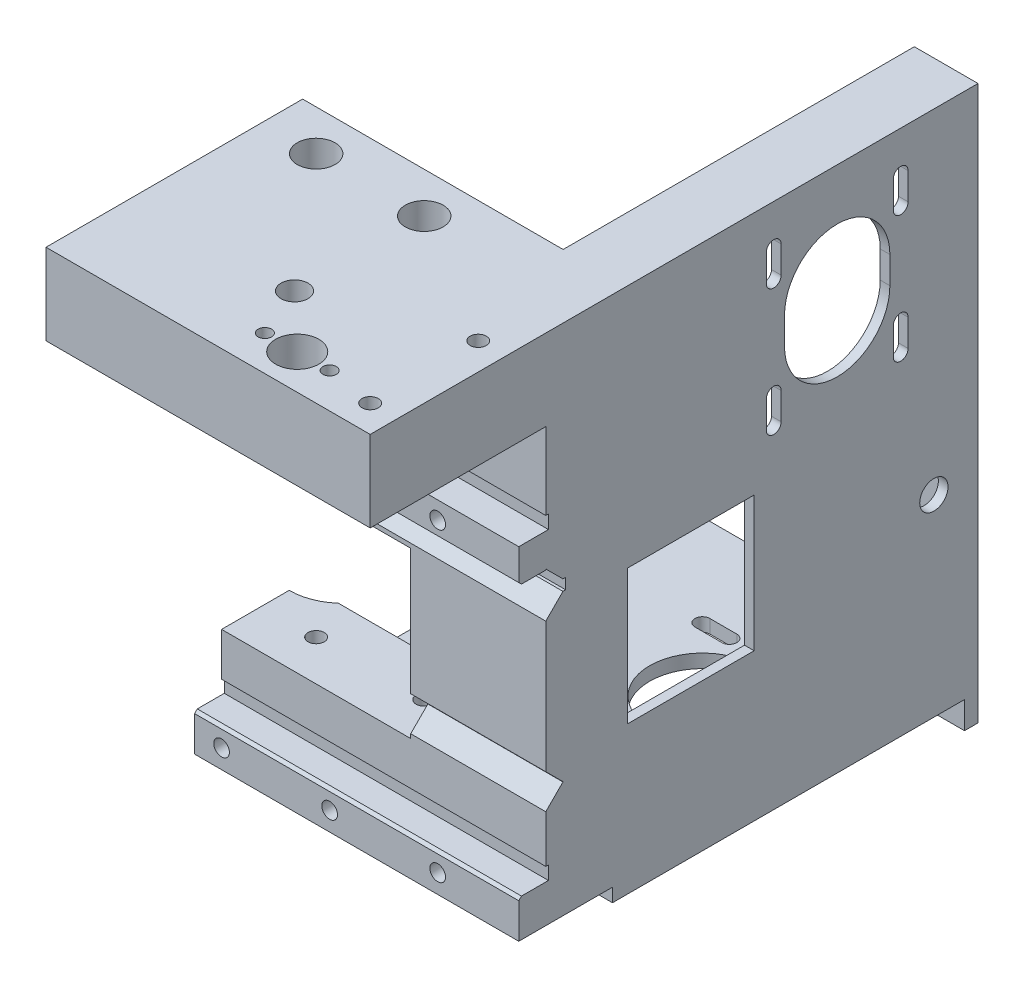
SolidWorks part; units mm, degrees
material "ABS"
ref_plane "Front Plane" through (0, 0, 0) normal (0, 0, 1) x (1, 0, 0)
ref_plane "Top Plane" through (0, 0, 0) normal (0, 1, 0) x (1, 0, 0)
ref_plane "Right Plane" through (0, 0, 0) normal (1, 0, 0) x (0, 0, -1)
sketch "Sketch1" plane through (0, 0, 0) normal (0, 0, 1) x (1, 0, 0)
  line L0 (-43.1034, -43.5723) -> (-43.1034, -8.5723)
  line L1 (-43.1034, 146.4277) -> (76.8966, 146.4277)
  line L2 (-43.1034, 146.4277) -> (-43.1034, 52.4277)
  line L3 (-43.1034, -43.5723) -> (76.8966, -43.5723)
  line L4 (76.8966, 146.4277) -> (76.8966, -43.5723)
  line L5 (-43.1034, 52.4277) -> (26.8966, 52.4277)
  line L7 (-43.1034, -8.5723) -> (26.8966, -8.5723)
  line L8 (26.8966, 52.4277) -> (26.8966, -8.5723)
  dimension "D1" = 61
  dimension "D2" = 190
  dimension "D3" = 35
  dimension "D4" = 120
  dimension "D6" = 70
extrude "Boss-Extrude1" add sketch "Sketch1" along normal blind 30
sketch "Sketch2" plane through (-43.1034, 0, 0) normal (-1, 0, 0) x (0, 0, 1)
  line L0 (30, 5.7917) -> (23.636, -0.5723)
  line L1 (30, 146.4277) -> (30, 52.4277) construction
  line L2 (23.636, -0.5723) -> (23.636, -0.6723)
  line L3 (23.636, -0.6723) -> (30, -7.0362)
  line L4 (30, -7.0362) -> (30, 5.7917)
  line L5 (30, -43.5723) -> (0, -43.5723) construction
  line L6 (30, 70.7917) -> (23.636, 64.4277)
  line L7 (30, -24.5723) -> (29, -24.5723)
  line L8 (30, -24.5723) -> (30, -29.5723)
  line L9 (30, -29.5723) -> (29, -29.5723)
  line L10 (29, -24.5723) -> (29, -29.5723)
  line L11 (23.636, 64.4277) -> (22.636, 64.4277)
  line L12 (22.636, 64.4277) -> (22.636, 60.4277)
  line L13 (22.636, 60.4277) -> (23.636, 60.4277)
  line L14 (23.636, 60.4277) -> (30, 54.0638)
  line L15 (30, 54.0638) -> (30, 70.7917)
  point P13 (29.5, -29.5723)
  dimension "D1" = 9
  dimension "D2" = 9
  dimension "D3" = 0.1
  dimension "D4" = 43
  dimension "D5" = 135
  dimension "D6" = 90
  dimension "D7" = 5
  dimension "D8" = 14
  dimension "D9" = 1
  dimension "D10" = 9
  dimension "D11" = 9
  dimension "D12" = 135
  dimension "D13" = 1
  dimension "D14" = 90
  dimension "D15" = 108
  dimension "D16" = 4
extrude "Cut-Extrude1" cut sketch "Sketch2" against normal blind 300
sketch "Sketch11" plane through (0, 0, 30) normal (0, 0, 1) x (1, 0, 0)
  line L0 (-43.1034, 146.4277) -> (-43.1034, 70.7917) construction
  line L1 (-43.1034, -29.5723) -> (76.8966, -29.5723)
  line L2 (-43.1034, -29.5723) -> (-43.1034, -43.5723)
  line L3 (-43.1034, -43.5723) -> (76.8966, -43.5723)
  line L4 (76.8966, -29.5723) -> (76.8966, -43.5723)
  line L5 (76.8966, 5.7917) -> (76.8966, 54.0638) construction
  line L6 (-43.1034, -43.5723) -> (76.8966, -43.5723) construction
  line L7 (76.8966, 82.9277) -> (-43.1034, 82.9277)
  line L8 (76.8966, 82.9277) -> (76.8966, 70.4277)
  line L9 (76.8966, 70.4277) -> (-43.1034, 70.4277)
  line L10 (-43.1034, 82.9277) -> (-43.1034, 70.4277)
  dimension "D1" = 14
  dimension "D2" = 12.5
  dimension "D3" = 100
extrude "Boss-Extrude2" add sketch "Sketch11" along normal blind 10
sketch "Sketch3" plane through (0, 146.4277, 0) normal (0, 1, 0) x (1, 0, 0)
  line L0 (-43.1034, -30) -> (-43.1034, 0) construction
  line L2 (76.8966, -30) -> (-43.1034, -30) construction
  circle A0 centre (-23.1034, -15) radius 3
  dimension "D1" = 20
  dimension "D2" = 15
extrude "Cut-Extrude2" cut sketch "Sketch3" against normal blind 1000
sketch "Sketch4" plane through (0, 146.4277, 0) normal (0, 1, 0) x (1, 0, 0)
  circle A0 centre (-23.1034, -15) radius 7
  circle A1 centre (-23.1034, -15) radius 3 construction
  dimension "D1" = 14
extrude "Cut-Extrude3" cut sketch "Sketch4" against normal blind 84
sketch "Sketch28" plane through (0, -43.5723, 0) normal (0, -1, 0) x (1, 0, 0)
  circle A0 centre (-23.1034, 15) radius 7
extrude "Cut-Extrude15" cut sketch "Sketch28" against normal blind 25 and the other way blind 10
pattern_linear "LPattern1" count 2 spacing 40 along (1, 0, 0) of "Cut-Extrude2", "Cut-Extrude3", "Cut-Extrude15"
sketch "Sketch7" plane through (0, 0, 0) normal (0, 0, -1) x (-1, 0, 0)
  line L0 (43.1034, -43.5723) -> (-76.8966, -43.5723) construction
  line L1 (43.1034, 146.4277) -> (43.1034, 52.4277) construction
  circle A0 centre (33.1034, -36.5723) radius 2.9002
  dimension "D1" = 7
  dimension "D2" = 10
extrude "Cut-Extrude6" cut sketch "Sketch7" against normal blind 40
sketch "Sketch8" plane through (0, 0, 0) normal (0, 0, -1) x (-1, 0, 0)
  circle A0 centre (33.1034, -36.5723) radius 5.871
extrude "Cut-Extrude7" cut sketch "Sketch8" against normal blind 25
pattern_linear "Линейный массив1" count 3 spacing 40 along (1, 0, 0) count 2 spacing 113 along (0, 1, 0) of "Cut-Extrude6", "Cut-Extrude7"
sketch "Эскиз1" plane through (-43.1034, 0, 0) normal (-1, 0, 0) x (0, 0, 1)
  line L1 (30, 82.9277) -> (29, 82.9277)
  line L2 (30, 82.9277) -> (30, 87.9277)
  line L3 (30, 87.9277) -> (29, 87.9277)
  line L4 (29, 82.9277) -> (29, 87.9277)
  dimension "D1" = 5
  dimension "D2" = 1
extrude "Вырез-Вытянуть1" cut sketch "Эскиз1" against normal blind 200
chamfer "Фаска1" distance 1 angle 45 2 edges at (16.8966, 70.4277, 40) (16.8966, -29.5723, 40)
sketch "Sketch12" plane through (0, 0, 0) normal (0, 0, -1) x (-1, 0, 0)
  line L0 (43.1034, -43.5723) -> (-76.8966, -43.5723) construction
  line L1 (-76.8966, 146.4277) -> (-73.328, 146.4277)
  line L2 (-76.8966, 146.4277) -> (-76.8966, -43.5723)
  line L3 (-76.8966, -43.5723) -> (-73.328, -43.5723)
  line L4 (-73.328, 146.4277) -> (-73.328, -43.5723)
extrude "Boss-Extrude3" add sketch "Sketch12" along normal blind 130
sketch "Sketch13" plane through (0, -43.5723, 0) normal (0, -1, 0) x (1, 0, 0)
  line L0 (76.8966, 40) -> (76.8966, -130) construction
  line L1 (76.8966, 5.3042) -> (-43.1034, 5.3042)
  line L2 (76.8966, 5.3042) -> (76.8966, -130)
  line L3 (76.8966, -130) -> (-43.1034, -130)
  line L4 (-43.1034, 5.3042) -> (-43.1034, -130)
  line L5 (-43.1034, 40) -> (-43.1034, 0) construction
extrude "Boss-Extrude4" add sketch "Sketch13" along normal blind 5
sketch "Sketch14" plane through (0, 0, 30) normal (0, 0, 1) x (1, 0, 0)
  line L0 (76.8966, 87.9277) -> (76.8966, 146.4277) construction
  line L1 (-43.1034, 146.4277) -> (76.8966, 146.4277)
  line L2 (-43.1034, 146.4277) -> (-43.1034, 116.4277)
  line L3 (-43.1034, 116.4277) -> (76.8966, 116.4277)
  line L4 (76.8966, 146.4277) -> (76.8966, 116.4277)
  dimension "D1" = 30
extrude "Boss-Extrude5" add sketch "Sketch14" along normal blind 65
sketch "Sketch16" plane through (73.328, 0, 0) normal (-1, 0, 0) x (0, 0, 1)
  line L0 (0, -43.5723) -> (0, 146.4277) construction
  line L1 (-130, 146.4277) -> (0, 146.4277)
  line L2 (-130, 146.4277) -> (-130, 141.4277)
  line L3 (-130, 141.4277) -> (0, 141.4277)
  line L4 (0, 146.4277) -> (0, 141.4277)
  dimension "D1" = 5
extrude "Boss-Extrude7" add sketch "Sketch16" along normal blind 20
sketch "Sketch17" plane through (73.328, 0, 0) normal (-1, 0, 0) x (0, 0, 1)
  line L0 (-130, -43.5723) -> (0, -43.5723) construction
  line L1 (-130, 141.4277) -> (-125, 141.4277)
  line L2 (-130, 141.4277) -> (-130, -43.5723)
  line L3 (-130, -43.5723) -> (-125, -43.5723)
  line L4 (-125, 141.4277) -> (-125, -43.5723)
  dimension "D1" = 5
extrude "Boss-Extrude8" add sketch "Sketch17" along normal blind 20
sketch "Sketch18" plane through (0, -43.5723, 0) normal (0, 1, 0) x (1, 0, 0)
  line L0 (76.8966, -95) -> (76.8966, 130) construction
  line L1 (-43.1034, 130) -> (76.8966, 130)
  line L2 (-43.1034, 130) -> (-43.1034, 125)
  line L3 (-43.1034, 125) -> (76.8966, 125)
  line L4 (76.8966, 130) -> (76.8966, 125)
extrude "Boss-Extrude9" add sketch "Sketch18" against normal blind 15
sketch "Sketch20" plane through (76.8966, 0, 0) normal (1, 0, 0) x (0, 0, -1)
  line L0 (101.3773, 131.4277) -> (101.3773, 121.4277) construction
  line L1 (104.1244, 131.4277) -> (104.1244, 121.4277)
  line L2 (98.6302, 131.4277) -> (98.6302, 121.4277)
  line L3 (77.8773, 107.9277) -> (77.8773, 97.9277) construction
  line L4 (97.3773, 107.9277) -> (97.3773, 97.9277)
  line L5 (58.3773, 107.9277) -> (58.3773, 97.9277)
  line L6 (-95, 146.4277) -> (130, 146.4277) construction
  line L7 (54.3773, 131.4277) -> (54.3773, 121.4277) construction
  line L8 (57.1244, 131.4277) -> (57.1244, 121.4277)
  line L9 (51.6302, 131.4277) -> (51.6302, 121.4277)
  line L10 (54.3773, 84.4277) -> (54.3773, 74.4277) construction
  line L11 (57.1244, 84.4277) -> (57.1244, 74.4277)
  line L12 (51.6302, 84.4277) -> (51.6302, 74.4277)
  line L13 (101.3773, 84.4277) -> (101.3773, 74.4277) construction
  line L14 (104.1244, 84.4277) -> (104.1244, 74.4277)
  line L15 (98.6302, 84.4277) -> (98.6302, 74.4277)
  arc A0 (104.1244, 131.4277) -> (98.6302, 131.4277) centre (101.3773, 131.4277) ccw
  arc A1 (98.6302, 121.4277) -> (104.1244, 121.4277) centre (101.3773, 121.4277) ccw
  arc A2 (97.3773, 107.9277) -> (58.3773, 107.9277) centre (77.8773, 107.9277) ccw
  arc A3 (58.3773, 97.9277) -> (97.3773, 97.9277) centre (77.8773, 97.9277) ccw
  arc A4 (57.1244, 131.4277) -> (51.6302, 131.4277) centre (54.3773, 131.4277) ccw
  arc A5 (51.6302, 121.4277) -> (57.1244, 121.4277) centre (54.3773, 121.4277) ccw
  arc A6 (57.1244, 84.4277) -> (51.6302, 84.4277) centre (54.3773, 84.4277) ccw
  arc A7 (51.6302, 74.4277) -> (57.1244, 74.4277) centre (54.3773, 74.4277) ccw
  arc A8 (104.1244, 84.4277) -> (98.6302, 84.4277) centre (101.3773, 84.4277) ccw
  arc A9 (98.6302, 74.4277) -> (104.1244, 74.4277) centre (101.3773, 74.4277) ccw
  point P2 (101.3773, 126.4277)
  point P9 (77.8773, 102.9277)
  point P20 (54.3773, 126.4277)
  point P27 (54.3773, 79.4277)
  point P34 (101.3773, 79.4277)
  dimension "D8" = 19.5
  dimension "D1" = 10
  dimension "D2" = 10
  dimension "D3" = 23.5
  dimension "D4" = 20
  dimension "D5" = 23.5
  dimension "D6" = 2
  dimension "D7" = 2
extrude "Cut-Extrude8" cut sketch "Sketch20" against normal blind 10
sketch "Sketch22" plane through (0, -48.5723, 0) normal (0, -1, 0) x (1, 0, 0)
  line L0 (8.7667, -49.1046) -> (18.7667, -49.1046) construction
  line L3 (8.7667, -46.3575) -> (18.7667, -46.3575)
  line L6 (8.7667, -51.8517) -> (18.7667, -51.8517)
  line L9 (32.2667, -72.6046) -> (42.2667, -72.6046) construction
  line L12 (32.2667, -53.1046) -> (42.2667, -53.1046)
  line L15 (32.2667, -92.1046) -> (42.2667, -92.1046)
  line L16 (8.7667, -96.1046) -> (18.7667, -96.1046) construction
  line L17 (8.7667, -93.3575) -> (18.7667, -93.3575)
  line L18 (8.7667, -98.8517) -> (18.7667, -98.8517)
  line L19 (55.7667, -96.1046) -> (65.7667, -96.1046) construction
  line L20 (55.7667, -93.3575) -> (65.7667, -93.3575)
  line L21 (55.7667, -98.8517) -> (65.7667, -98.8517)
  line L22 (55.7667, -49.1046) -> (65.7667, -49.1046) construction
  line L23 (55.7667, -46.3575) -> (65.7667, -46.3575)
  line L24 (55.7667, -51.8517) -> (65.7667, -51.8517)
  arc A10 (8.7667, -46.3575) -> (8.7667, -51.8517) centre (8.7667, -49.1046) ccw
  arc A11 (18.7667, -51.8517) -> (18.7667, -46.3575) centre (18.7667, -49.1046) ccw
  arc A12 (32.2667, -53.1046) -> (32.2667, -92.1046) centre (32.2667, -72.6046) ccw
  arc A13 (42.2667, -92.1046) -> (42.2667, -53.1046) centre (42.2667, -72.6046) ccw
  arc A14 (8.7667, -93.3575) -> (8.7667, -98.8517) centre (8.7667, -96.1046) ccw
  arc A15 (18.7667, -98.8517) -> (18.7667, -93.3575) centre (18.7667, -96.1046) ccw
  arc A16 (55.7667, -93.3575) -> (55.7667, -98.8517) centre (55.7667, -96.1046) ccw
  arc A17 (65.7667, -98.8517) -> (65.7667, -93.3575) centre (65.7667, -96.1046) ccw
  arc A18 (55.7667, -46.3575) -> (55.7667, -51.8517) centre (55.7667, -49.1046) ccw
  arc A19 (65.7667, -51.8517) -> (65.7667, -46.3575) centre (65.7667, -49.1046) ccw
  point P2 (13.7667, -49.1046)
  point P9 (37.2667, -72.6046)
  point P16 (13.7667, -96.1046)
  point P23 (60.7667, -96.1046)
  point P30 (60.7667, -49.1046)
  dimension "D5" = 19.5
  dimension "D1" = 10
  dimension "D2" = 10
  dimension "D3" = 23.5
  dimension "D4" = 23.5
extrude "Cut-Extrude10" cut sketch "Sketch22" against normal blind 10
sketch "Sketch23" plane through (0, 116.4277, 0) normal (0, -1, 0) x (1, 0, 0)
  line L0 (-43.1034, 95) -> (-43.1034, 30) construction
  line L3 (-43.1034, 30) -> (76.8966, 30) construction
  circle A0 centre (16.8966, 63) radius 25
  dimension "D1" = 50
  dimension "D2" = 60
  dimension "D3" = 33
extrude "Cut-Extrude11" cut sketch "Sketch23" against normal blind 10.5
sketch "Sketch24" plane through (0, 126.9277, 0) normal (0, -1, 0) x (1, 0, 0)
  circle A0 centre (16.8966, 63) radius 5
extrude "Cut-Extrude12" cut sketch "Sketch24" against normal blind 100
sketch "Sketch25" plane through (0, 116.4277, 0) normal (0, -1, 0) x (1, 0, 0)
  line L1 (-43.1034, 95) -> (-43.1034, 30) construction
  line L3 (-43.1034, 95) -> (76.8966, 95) construction
  circle A0 centre (36.8966, 82) radius 8
  dimension "D1" = 16
  dimension "D2" = 80
  dimension "D3" = 13
extrude "Cut-Extrude13" cut sketch "Sketch25" against normal blind 100 contours A0
sketch "Sketch26" plane through (0, -48.5723, 0) normal (0, -1, 0) x (1, 0, 0)
  line L1 (-43.1034, 30) -> (76.8966, 30) construction
  line L2 (-43.1034, 30) -> (-43.1034, 0) construction
  circle A0 centre (-43.1034, -15) radius 20
  dimension "D2" = 40
  dimension "D1" = 45
extrude "Cut-Extrude14" cut sketch "Sketch26" against normal blind 100 from offset 5 offset against normal yes
sketch "Эскиз2" plane through (0, 146.4277, 0) normal (0, 1, 0) x (1, 0, 0)
  line L0 (76.8966, -95) -> (-43.1034, -95) construction
  circle A0 centre (24.8966, -82) radius 2.5
  circle A2 centre (36.8966, -82) radius 8 construction
  dimension "D2" = 5
  dimension "D1" = 12
  dimension "D3" = 13
extrude "Вырез-Вытянуть2" cut sketch "Эскиз2" against normal blind 10
pattern_circular "Круговой массив1" count 2 over 360 about axis through (36.8966, 146.4277, 82) along (0, -1, 0) of "Вырез-Вытянуть2"
sketch "Эскиз4" plane through (0, 116.4277, 0) normal (0, -1, 0) x (1, 0, 0)
  circle A0 centre (36.8966, 82) radius 10
extrude "Вырез-Вытянуть3" cut sketch "Эскиз4" against normal blind 10.5
sketch "Sketch27" plane through (0, -48.5723, 0) normal (0, -1, 0) x (-1, 0, 0)
  line L0 (43.1034, -5.3042) -> (43.1034, 125) construction
  line L1 (43.1034, -5.3042) -> (38.1034, -5.3042)
  line L2 (43.1034, -5.3042) -> (43.1034, 125)
  line L3 (43.1034, 125) -> (38.1034, 125)
  line L4 (38.1034, -5.3042) -> (38.1034, 125)
  line L5 (43.1034, 125) -> (-76.8966, 125) construction
  line L6 (-76.8966, -5.3042) -> (22.9942, -5.3042) construction
  dimension "D1" = 5
extrude "Boss-Extrude10" add sketch "Sketch27" along normal blind 10
chamfer "Chamfer3" distance 10 angle 45 1 edges at (-38.1034, -48.5723, -59.8479)
sketch "Sketch29" plane through (0, 146.4277, 0) normal (0, 1, 0) x (1, 0, 0)
  line L0 (76.8966, -95) -> (76.8966, 130) construction
  line L1 (76.8966, -95) -> (-43.1034, -95) construction
  circle A0 centre (66.8966, -85) radius 3
  dimension "D1" = 10
  dimension "D2" = 10
extrude "Cut-Extrude16" cut sketch "Sketch29" against normal blind 50
pattern_linear "LPattern2" count 2 spacing 40 along (0, 0, -1) of "Cut-Extrude16"
sketch "Sketch30" plane through (76.8966, 0, 0) normal (1, 0, 0) x (0, 0, -1)
  line L1 (0.2595, 55.9322) -> (47.1281, 55.9322)
  line L2 (0.2595, 55.9322) -> (0.2595, 5.9987)
  line L3 (0.2595, 5.9987) -> (47.1281, 5.9987)
  line L4 (47.1281, 55.9322) -> (47.1281, 5.9987)
extrude "Cut-Extrude17" cut sketch "Sketch30" against normal blind 50
sketch "Sketch31" plane through (73.328, 0, 0) normal (-1, 0, 0) x (0, 0, 1)
  line L0 (-47.1281, 55.9322) -> (-0.2595, 55.9322) construction
  line L1 (-52.4918, 61.2959) -> (0.2513, 61.2959)
  line L2 (-52.4918, 61.2959) -> (-52.4918, 55.9322)
  line L3 (-52.4918, 55.9322) -> (0.2513, 55.9322)
  line L4 (0.2513, 61.2959) -> (0.2513, 55.9322)
sketch "Sketch32" plane through (76.8966, 0, 0) normal (1, 0, 0) x (0, 0, -1)
  circle A0 centre (113.6635, 22.7283) radius 5.236
extrude "Cut-Extrude18" cut sketch "Sketch32" against normal blind 150
sketch "Sketch33" plane through (-43.1034, 0, 0) normal (-1, 0, 0) x (0, 0, 1)
  line L1 (5.3042, -58.5723) -> (-38.444, -58.5723)
  line L2 (5.3042, -58.5723) -> (5.3042, -51.8526)
  line L3 (5.3042, -51.8526) -> (-38.444, -51.8526)
  line L4 (-38.444, -58.5723) -> (-38.444, -51.8526)
extrude "Boss-Extrude12" add sketch "Sketch33" along normal blind 20
sketch "Sketch34" plane through (0, -58.5723, 0) normal (0, -1, 0) x (1, 0, 0)
  circle A0 centre (-58.7576, -15.818) radius 3.7611
extrude "Cut-Extrude19" cut sketch "Sketch34" against normal blind 20
sketch "Sketch35" plane through (0, 0, 30) normal (0, 0, 1) x (1, 0, 0)
  line L1 (-43.1034, 116.4277) -> (-37.3059, 116.4277)
  line L2 (-43.1034, 116.4277) -> (-43.1034, 102.1622)
  line L3 (-43.1034, 102.1622) -> (-37.3059, 102.1622)
  line L4 (-37.3059, 116.4277) -> (-37.3059, 102.1622)
extrude "Boss-Extrude13" add sketch "Sketch35" along normal blind 20
chamfer "Chamfer4" distance 20 angle 45 1 edges at (-37.3059, 109.295, 30)
sketch "Sketch36" plane through (-43.1034, 0, 0) normal (-1, 0, 0) x (0, 0, 1)
  circle A0 centre (40.0959, 109.8246) radius 4.9953
extrude "Cut-Extrude20" cut sketch "Sketch36" against normal blind 20
sketch "Sketch37" plane through (-43.1034, 0, 0) normal (-1, 0, 0) x (0, 0, 1)
  circle A0 centre (40.0959, 109.8246) radius 6.6604
extrude "Cut-Extrude21" cut sketch "Sketch37" against normal blind 20 from offset 5 offset against normal yes
ref_plane "Plane1" through (-96.672, 0, 0) normal (-1, 0, 0) x (0, 0, 1)
sketch "Sketch38" plane through (-96.672, 0, 0) normal (-1, 0, 0) x (0, 0, 1)
  line L1 (-98.5539, 56.8722) -> (-60.6206, 56.8722)
  line L2 (-98.5539, 56.8722) -> (-98.5539, 40.0564)
  line L3 (-98.5539, 40.0564) -> (-60.6206, 40.0564)
  line L4 (-60.6206, 56.8722) -> (-60.6206, 40.0564)
sketch "Sketch39" plane through (0, 0, -52.4918) normal (0, 0, -1) x (-1, 0, 0)
  line L0 (43.1034, 61.2959) -> (-73.328, 61.2959) construction
  line L1 (-32.3472, 61.2959) -> (76.672, 61.2959)
  line L2 (-32.3472, 61.2959) -> (-32.3472, 55.9322)
  line L3 (-32.3472, 55.9322) -> (76.672, 55.9322)
  line L4 (76.672, 61.2959) -> (76.672, 55.9322)
sketch "Sketch42" plane through (-96.672, 0, 0) normal (-1, 0, 0) x (0, 0, 1)
  line L0 (-98.5539, 56.8722) -> (-98.5539, 40.0564) construction
  line L1 (-115.7607, 64.172) -> (-98.5539, 64.172)
  line L2 (-115.7607, 64.172) -> (-115.7607, 40.0564)
  line L3 (-115.7607, 40.0564) -> (-98.5539, 40.0564)
  line L4 (-98.5539, 64.172) -> (-98.5539, 40.0564)
sketch "Sketch43" plane through (73.328, 0, 0) normal (-1, 0, 0) x (0, 0, 1)
  line L1 (-123.7123, 56.3507) -> (-116.9339, 56.3507)
  line L2 (-123.7123, 56.3507) -> (-123.7123, 41.36)
  line L3 (-123.7123, 41.36) -> (-116.9339, 41.36)
  line L4 (-116.9339, 56.3507) -> (-116.9339, 41.36)
sketch "Sketch40" plane through (-96.672, 0, 0) normal (-1, 0, 0) x (0, 0, 1)
  circle A0 centre (-80.1739, 48.008) radius 4.5
extrude "Cut-Extrude22" cut sketch "Sketch40" against normal blind 100 rebuild error yes
sketch "Sketch41" plane through (-96.672, 0, 0) normal (-1, 0, 0) x (0, 0, 1)
  circle A0 centre (-80.1739, 48.008) radius 6.6468
extrude "Cut-Extrude23" cut sketch "Sketch41" against normal blind 100 from offset 5 rebuild error yes offset against normal yes
extrude "Cut-Extrude24" cut sketch "Sketch42" against normal blind 100 rebuild error yes
